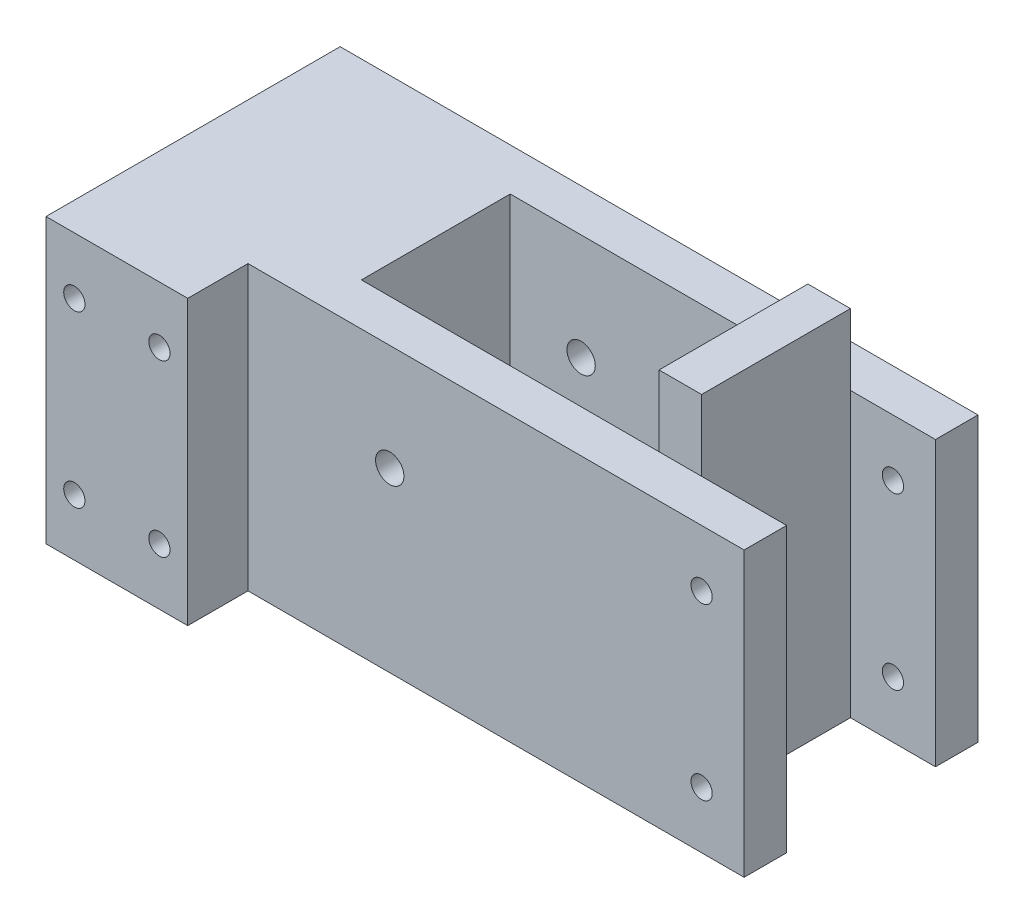
SolidWorks part; units mm, degrees
ref_plane "前视基准面" through (0, 0, 0) normal (0, 0, 1) x (1, 0, 0)
ref_plane "上视基准面" through (0, 0, 0) normal (0, 1, 0) x (1, 0, 0)
ref_plane "右视基准面" through (0, 0, 0) normal (1, 0, 0) x (0, 0, -1)
other "Configuration Table"
sketch "草图1" plane through (0, 0, 0) normal (0, 1, 0) x (1, 0, 0)
  line L1 (0, 0) -> (90, 0)
  line L3 (0, 33) -> (90, 33)
  line L9 (0, 33) -> (0, 0)
  line L10 (90, 33) -> (90, 27)
  line L11 (90, 27) -> (30, 27)
  line L12 (30, 27) -> (30, 6)
  line L13 (30, 6) -> (90, 6)
  line L14 (90, 6) -> (90, 0)
  dimension "D1" = 21
  dimension "D2" = 60
  dimension "D3" = 6
  dimension "D4" = 6
  dimension "D5" = 90
extrude "凸台-拉伸1" add sketch "草图1" along normal blind 40
sketch "草图7" plane through (0, 40, 0) normal (0, 1, 0) x (1, 0, 0)
  line L1 (20, -8.5) -> (0, -8.5)
  line L2 (20, -8.5) -> (20, 0)
  line L3 (20, 0) -> (0, 0)
  line L4 (0, -8.5) -> (0, 0)
  line L6 (0, 0) -> (90, 0) construction
  line L7 (0, 33) -> (0, 0) construction
  dimension "D1" = 8.5
  dimension "D2" = 20
extrude "凸台-拉伸5" add sketch "草图7" against normal up to surface (40 mm away) up to face at (52.5, 0, -16.5)
sketch "草图8" plane through (0, 0, -33) normal (0, 0, -1) x (-1, 0, 0)
  line L0 (-90, 40) -> (-90, 0) construction
  line L1 (-84, 32) -> (-16, 32) construction
  line L2 (-84, 32) -> (-84, 8) construction
  line L3 (-84, 8) -> (-16, 8) construction
  line L4 (-16, 32) -> (-16, 8) construction
  line L5 (-90, 40) -> (0, 40) construction
  circle A0 centre (-84, 8) radius 1.5
  circle A1 centre (-84, 32) radius 1.5
  circle A2 centre (-16, 32) radius 1.5
  circle A3 centre (-16, 8) radius 1.5
  dimension "D4" = 3
  dimension "D1" = 68
  dimension "D2" = 24
  dimension "D3" = 6
  dimension "D5" = 8
extrude "切除-拉伸2" cut sketch "草图8" against normal through all
sketch "草图9" plane through (0, 0, 8.5) normal (0, 0, 1) x (1, 0, 0)
  line L0 (4, 32) -> (16, 32) construction
  line L1 (4, 8) -> (16, 8) construction
  circle A0 centre (4, 32) radius 1.5
  circle A1 centre (4, 8) radius 1.5
  circle A3 centre (16, 32) radius 1.5 construction
  circle A4 centre (16, 8) radius 1.5 construction
  dimension "D1" = 3
  dimension "D2" = 3
  dimension "D3" = 12
extrude "切除-拉伸3" cut sketch "草图9" against normal through all
sketch "草图10" plane through (0, 40, 0) normal (0, 1, 0) x (1, 0, 0)
  line L0 (30, 27) -> (90, 27) construction
  line L1 (78, 27) -> (72, 27)
  line L2 (78, 27) -> (78, 6)
  line L3 (78, 6) -> (72, 6)
  line L4 (72, 27) -> (72, 6)
  line L5 (90, 6) -> (30, 6) construction
  line L7 (30, 6) -> (30, 27) construction
  dimension "D1" = 42
  dimension "D2" = 6
extrude "凸台-拉伸6" add sketch "草图10" along direction (0, 1, 0) on the side against the normal up to surface (40 mm away) and the other way blind 10 up to face at (46, 0, -11.5)
sketch "草图11" plane through (0, 0, 0) normal (0, 0, 1) x (1, 0, 0)
  line L0 (20, 0) -> (90, 0) construction
  line L1 (20, 0) -> (20, 40) construction
  circle A0 centre (40, 25) radius 2
  dimension "D2" = 4
  dimension "D1" = 25
  dimension "D3" = 20
extrude "切除-拉伸4" cut sketch "草图11" against normal through all
